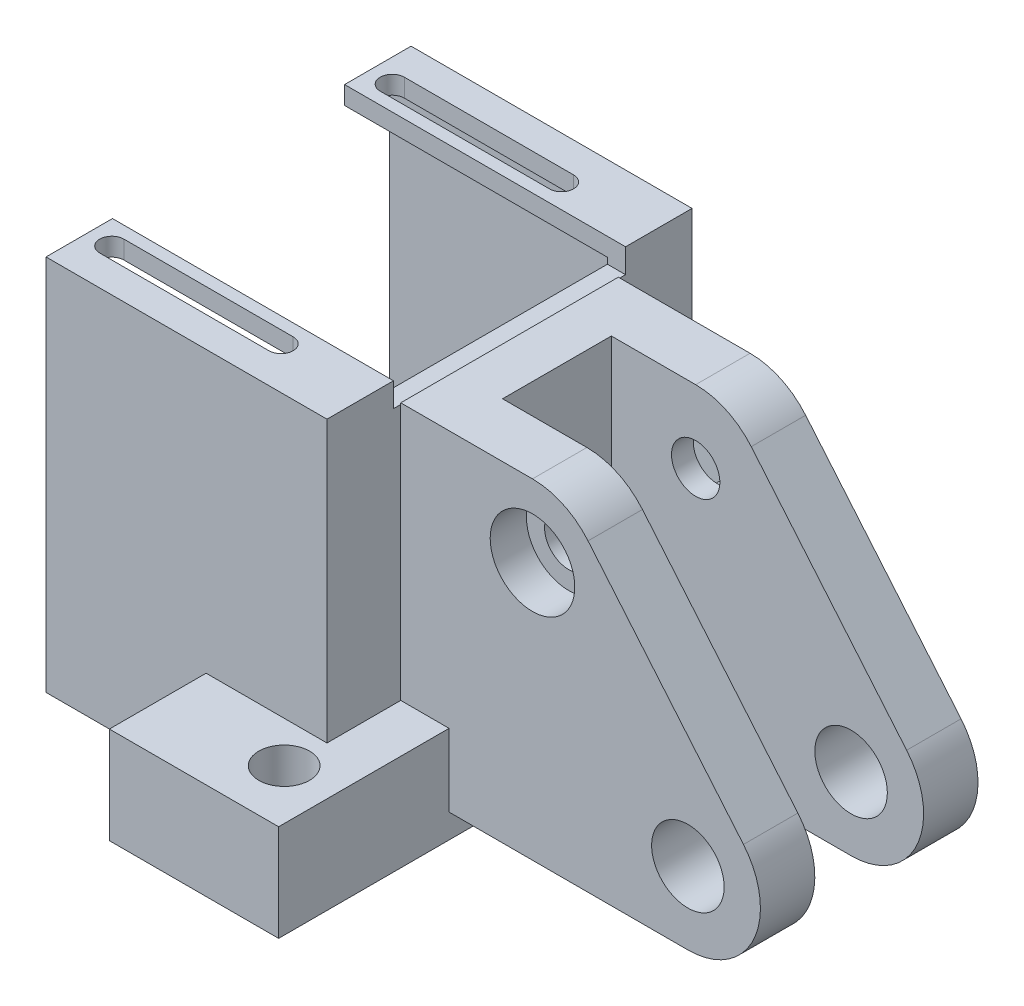
SolidWorks part; units mm, degrees
material "Vero PureWhite"
ref_plane "前视基准面" through (0, 0, 0) normal (0, 0, 1) x (1, 0, 0)
ref_plane "上视基准面" through (0, 0, 0) normal (0, 1, 0) x (1, 0, 0)
ref_plane "右视基准面" through (0, 0, 0) normal (1, 0, 0) x (0, 0, -1)
other "Configuration Table"
sketch "草图1" plane through (0, 0, 0) normal (0, 0, 1) x (1, 0, 0)
  line L0 (0, 0) -> (-71.912, 0) construction
  line L1 (0, 0) -> (-12.8558, 15.3209) construction
  line L2 (-8.2595, 19.1776) -> (4.5963, 3.8567)
  line L3 (-12.8558, 21.3209) -> (-47, 21.3209)
  line L4 (0, -6) -> (-47, -6)
  line L5 (-47, 21.3209) -> (-47, -6)
  arc A0 (0, -6) -> (4.5963, 3.8567) centre (0, 0) ccw
  arc A1 (-12.8558, 21.3209) -> (-8.2595, 19.1776) centre (-12.8558, 15.3209) cw
  dimension "D3" = 47
  dimension "D1" = 50
  dimension "D2" = 20
extrude "凸台-拉伸1" add sketch "草图1" along normal mid plane 18
sketch "草图2" plane through (0, 0, 0) normal (0, 0, 1) x (1, 0, 0)
  line L0 (-19.8321, -6) -> (-19.8321, 21.3209)
  line L1 (-12.8558, 21.3209) -> (-47, 21.3209) construction
  line L5 (-47, -6) -> (0, -6) construction
  line L6 (-19.8321, -6) -> (7.7338, -6)
  line L7 (7.7338, -6) -> (7.7338, 21.3209)
  line L9 (-19.8321, 21.3209) -> (7.7338, 21.3209)
extrude "切除-拉伸1" cut sketch "草图2" against normal mid plane 9
ref_plane "基准面1" through (0, 0, 0) normal (0.766, 0.6428, 0) x (-0.6428, 0.766, 0)
sketch "草图3" plane through (0, 0, 0) normal (0.766, 0.6428, 0) x (-0.6428, 0.766, 0)
  line L0 (19.9997, -10) -> (19.9997, 8.1) construction
  line L1 (18.5997, -10) -> (21.3997, -10) construction
  line L2 (19.9997, -9) -> (17.4997, -9)
  line L3 (46.5438, -9) -> (25.6148, -9) construction
  line L4 (25.6148, -9) -> (-4.5963, -9) construction
  line L5 (17.4997, -9) -> (17.4997, -6.3)
  line L6 (17.4997, -6.3) -> (17.9997, -6.3)
  line L7 (17.9997, -6.3) -> (17.9997, 6)
  line L8 (17.9997, 6) -> (16.4997, 6)
  line L9 (16.4997, 6) -> (16.4997, 9)
  line L10 (25.6148, 9) -> (-4.5963, 9) construction
  line L11 (16.4997, 9) -> (19.9997, 9)
  line L12 (46.5438, 9) -> (25.6148, 9) construction
  line L13 (29.0806, 4.5) -> (8.1515, 4.5) construction
  line L14 (18.0997, -6) -> (21.8997, -6) construction
  line L15 (19.9997, -9) -> (19.9997, 9)
  dimension "D1" = 4
  dimension "D2" = 7
  dimension "D3" = 1.5
  dimension "D4" = 0.3
  dimension "D5" = 5
revolve "切除-旋转1" cut sketch "草图3" angle 360 about L0
sketch "草图4" plane through (0, 0, -9) normal (0, 0, -1) x (-1, 0, 0)
  line L7 (11.7697, 18.3047) -> (9.7284, 15.8723)
  line L8 (9.7284, 15.8723) -> (10.8142, 12.8883)
  line L9 (10.8142, 12.8883) -> (13.9414, 12.3366)
  line L10 (13.9414, 12.3366) -> (15.9827, 14.769)
  line L11 (15.9827, 14.769) -> (14.8969, 17.753)
  line L12 (14.8969, 17.753) -> (11.7697, 18.3047)
  circle A0 centre (12.8556, 15.3207) radius 2.75 construction
  dimension "D1" = 5.5
extrude "切除-拉伸2" cut sketch "草图4" against normal up to surface (2.7 mm away) up to face at (-15.3556, 15.3207, -6.3)
sketch "草图5" plane through (0, 0, 9) normal (0, 0, 1) x (1, 0, 0)
  circle A0 centre (0, 0) radius 3
  dimension "D1" = 6
extrude "切除-拉伸3" cut sketch "草图5" against normal through all
sketch "草图8" plane through (0, 21.3209, 0) normal (0, 1, 0) x (1, 0, 0)
  line L0 (-23.7558, 9) -> (-23.7558, -9)
  line L1 (-12.8558, 9) -> (-47, 9) construction
  line L2 (-12.8558, -9) -> (-47, -9) construction
  line L3 (-23.7558, -9) -> (-47, -9)
  line L4 (-47, -9) -> (-47, 9)
  line L5 (-47, 9) -> (-23.7558, 9)
  line L6 (-25.2558, 12.6) -> (-25.2558, -12.6) construction
  dimension "D1" = 1.5
extrude "凸台-拉伸2" add sketch "草图8" along normal offset from surface (1.8791 mm away) 2 offset beyond the face yes
sketch "草图9" plane through (0, -6, 0) normal (0, -1, 0) x (1, 0, 0)
  line L0 (-23.7558, 9) -> (-47, 9) construction
  line L1 (-23.7558, -9) -> (-23.7558, 9) construction
  line L2 (-47, -9) -> (-23.7558, -9) construction
  line L3 (-47, 9) -> (-47, -9) construction
  line L4 (-23.7558, 9) -> (-47, 9)
  line L5 (-23.7558, -9) -> (-23.7558, 9)
  line L6 (-47, -9) -> (-23.7558, -9)
  line L7 (-47, 9) -> (-47, -9)
extrude "凸台-拉伸3" add sketch "草图9" along normal offset from surface (2 mm away) 2 offset beyond the face yes
sketch "草图10" plane through (0, 0, 9) normal (0, 0, 1) x (1, 0, 0)
  line L0 (-47, 23.2) -> (-23.7558, 23.2)
  line L1 (-23.7558, 23.2) -> (-23.7558, -8)
  line L2 (-23.7558, -8) -> (-47, -8)
  line L3 (-47, -8) -> (-47, 23.2)
extrude "凸台-拉伸4" add sketch "草图10" along normal offset from surface (6.1 mm away) 2 offset beyond the face yes
sketch "草图11" plane through (0, 0, -9) normal (0, 0, -1) x (-1, 0, 0)
  line L4 (47, 23.2) -> (23.7558, 23.2)
  line L5 (23.7558, 23.2) -> (23.7558, -8)
  line L6 (23.7558, -8) -> (47, -8)
  line L7 (47, -8) -> (47, 23.2)
  line L8 (47, 23.2) -> (23.7558, 23.2)
  line L9 (23.7558, 23.2) -> (23.7558, -8)
  line L10 (23.7558, -8) -> (47, -8)
  line L11 (47, -8) -> (47, 23.2)
  dimension "D1" = 0
extrude "凸台-拉伸5" add sketch "草图11" along normal offset from surface (6.1 mm away) 2 offset beyond the face yes
shell "抽壳2" thickness 1.5 removed face at (-47, 7.6, 0)
sketch "草图12" plane through (0, -8, 0) normal (0, -1, 0) x (1, 0, 0)
  line L0 (-23.7558, -15.1) -> (-23.7558, 15.1) construction
  line L1 (-23.7558, 15.1) -> (-47, 15.1) construction
  line L2 (-23.7558, -15.1) -> (-47, -15.1) construction
  line L4 (-45.0558, 12.6) -> (-31.0558, 12.6)
  line L5 (-45.0558, 10.6) -> (-31.0558, 10.6)
  line L6 (-45.0558, -10.6) -> (-31.0558, -10.6)
  line L7 (-45.0558, -12.6) -> (-31.0558, -12.6)
  arc A8 (-31.0558, -12.6) -> (-31.0558, -10.6) centre (-31.0558, -11.6) ccw
  arc A9 (-31.0558, 10.6) -> (-31.0558, 12.6) centre (-31.0558, 11.6) ccw
  arc A10 (-45.0558, 12.6) -> (-45.0558, 10.6) centre (-45.0558, 11.6) ccw
  arc A11 (-45.0558, -10.6) -> (-45.0558, -12.6) centre (-45.0558, -11.6) ccw
  dimension "D2" = 7.3
  dimension "D3" = 2
  dimension "D4" = 2
  dimension "D7" = 2
  dimension "D8" = 2
  dimension "D1" = 7.3
  dimension "D5" = 21.3
  dimension "D6" = 21.3
  dimension "D9" = 3.5
  dimension "D10" = 3.5
  dimension "D11" = 3.5
  dimension "D12" = 3.5
extrude "切除-拉伸4" cut sketch "草图12" against normal through all
sketch "草图13" plane through (0, 23.2, 0) normal (0, 1, 0) x (1, 0, 0)
  line L0 (-47, 9.6) -> (-23.7558, 9.6)
  line L1 (-47, 15.1) -> (-47, -15.1) construction
  line L2 (-23.7558, -15.1) -> (-23.7558, 15.1) construction
  line L3 (-47, -9.6) -> (-23.7558, -9.6)
  line L4 (-47, 15.1) -> (-23.7558, 15.1) construction
  line L5 (-47, -15.1) -> (-23.7558, -15.1) construction
  line L6 (-47, 9.6) -> (-47, -9.6)
  line L7 (-23.7558, 9.6) -> (-23.7558, -9.6)
  dimension "D1" = 5.5
  dimension "D2" = 5.5
extrude "切除-拉伸5" cut sketch "草图13" against normal up to surface (2 mm away)
sketch "草图15" plane through (0, 0, 15.1) normal (0, 0, 1) x (1, 0, 0)
  line L0 (-33.7558, -8) -> (-33.7558, 0)
  line L1 (-23.7558, -8) -> (-47, -8) construction
  line L2 (-33.7558, 0) -> (-23.7558, 0)
  line L3 (-23.7558, 23.2) -> (-23.7558, -8) construction
  line L4 (-23.7558, 0) -> (-23.7558, -8)
  line L5 (-23.7558, -8) -> (-33.7558, -8)
  dimension "D1" = 8
  dimension "D2" = 10
extrude "凸台-拉伸6" add sketch "草图15" along normal blind 8
mirror "镜向1" about plane through (0, 0, 0) normal (0, 0, 1) of "凸台-拉伸6"
sketch "草图14" plane through (0, -8, 0) normal (0, -1, 0) x (1, 0, 0)
  line L0 (-23.7558, 0) -> (-101.3548, 0) construction
  line L1 (-23.7558, -9) -> (-23.7558, 9) construction
  circle A0 centre (-101.3548, 0) radius 20
  circle A1 centre (-23.897, 18.5) radius 18.5
  circle A2 centre (-23.897, -18.5) radius 18.5
  circle A3 centre (-48.1458, 0) radius 12
  circle A4 centre (-23.897, 18.5) radius 3.5
  circle A5 centre (-23.897, -18.5) radius 3.5
  circle A6 centre (-23.897, 18.5) radius 2.1
  circle A7 centre (-23.897, -18.5) radius 2.1
  dimension "D1" = 40
  dimension "D2" = 24
  dimension "D3" = 7
  dimension "D4" = 7
  dimension "D5" = 37
  dimension "D6" = 4.2
  dimension "D7" = 4.2
sketch "草图19" plane through (0, 0, 0) normal (0, 0, 1) x (1, 0, 0)
  line L0 (-19.7558, -8) -> (-19.7558, 0)
  line L2 (-42.397, -8) -> (-5.397, -8) construction
  line L3 (-23.7558, 23.2) -> (-23.7558, 0) construction
  line L4 (-23.7558, 0) -> (-19.7558, 0)
  line L5 (-23.7558, 0) -> (-23.7558, -8)
  line L6 (-23.7558, -8) -> (-19.7558, -8)
  line L7 (-23.7558, 0) -> (-33.7558, 0) construction
  dimension "D1" = 4
extrude "凸台-拉伸7" add sketch "草图19" along normal up to surface and the other way up to surface up to face at (-28.7558, -4, 23.1) other way up to face at (-28.7558, -4, -23.1)
sketch "草图17" plane through (0, -8, 0) normal (0, -1, 0) x (1, 0, 0)
  circle A0 centre (-23.897, 18.5) radius 2.1 construction
  circle A1 centre (-23.897, 18.5) radius 2.1
  circle A2 centre (-23.897, -18.5) radius 2.1 construction
  circle A3 centre (-23.897, -18.5) radius 2.1
extrude "切除-拉伸6" cut sketch "草图17" against normal through all
sketch "草图20" plane through (0, 0, -13.6) normal (0, 0, 1) x (1, 0, 0)
  line L4 (-47, -6.5) -> (-25.2558, -6.5)
  line L5 (-25.2558, -6.5) -> (-25.2558, 21.7)
  line L6 (-25.2558, 21.7) -> (-47, 21.7)
  line L7 (-47, 21.7) -> (-47, -6.5)
  line L8 (-47, -6.5) -> (-25.2558, -6.5)
  line L9 (-25.2558, -6.5) -> (-25.2558, 21.7)
  line L10 (-25.2558, 21.7) -> (-47, 21.7)
  line L11 (-47, 21.7) -> (-47, -6.5)
  dimension "D1" = 0
extrude "凸台-拉伸8" add sketch "草图20" along normal blind 0.3
sketch "草图21" plane through (0, 0, 13.6) normal (0, 0, -1) x (-1, 0, 0)
  line L4 (25.2558, -6.5) -> (47, -6.5)
  line L5 (47, -6.5) -> (47, 21.7)
  line L6 (47, 21.7) -> (25.2558, 21.7)
  line L7 (25.2558, 21.7) -> (25.2558, -6.5)
  line L8 (25.2558, -6.5) -> (47, -6.5)
  line L9 (47, -6.5) -> (47, 21.7)
  line L10 (47, 21.7) -> (25.2558, 21.7)
  line L11 (25.2558, 21.7) -> (25.2558, -6.5)
  dimension "D1" = 0
extrude "凸台-拉伸9" add sketch "草图21" along normal blind 0.3
sketch "草图22" plane through (0, -8, 0) normal (0, -1, 0) x (1, 0, 0)
  line L0 (-47, 9) -> (-40.2085, 9)
  line L1 (-23.7558, 9) -> (-47, 9) construction
  line L2 (-40.2085, 9) -> (-40.2085, -9)
  line L3 (-47, -9) -> (-23.7558, -9) construction
  line L4 (-40.2085, -9) -> (-47, -9)
  line L5 (-47, -9) -> (-47, 9)
  line L6 (-47, 9) -> (-47, -9) construction
  circle A0 centre (-48.1458, 0) radius 12 construction
  point P7 (-47, 8.9677)
extrude "切除-拉伸7" cut sketch "草图22" against normal up to next
